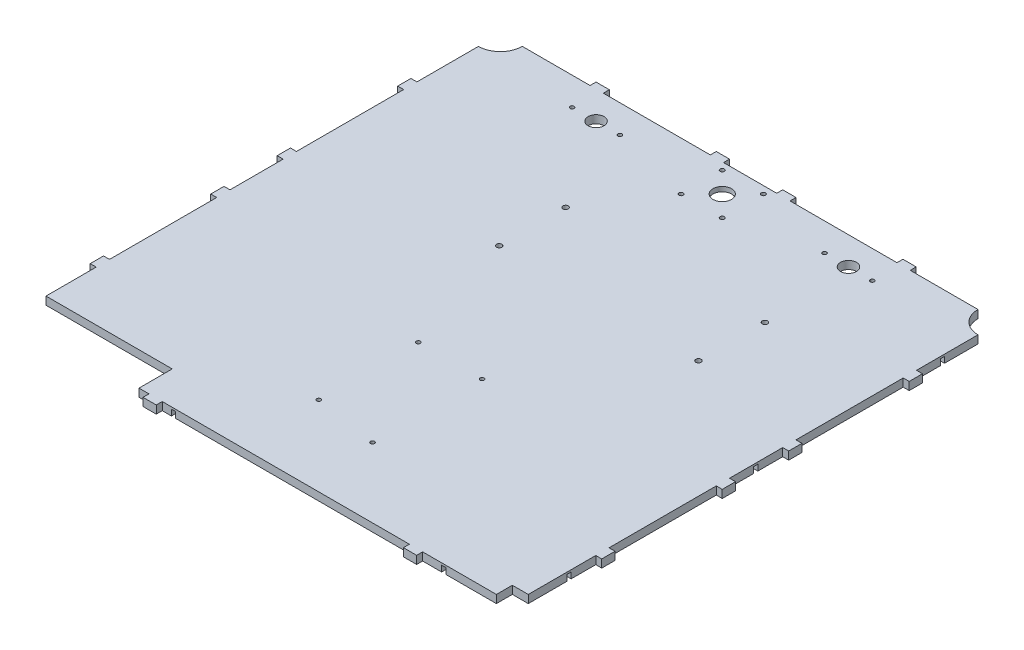
SolidWorks part; units mm, degrees
ref_plane "Alzado" through (0, 0, 0) normal (0, 0, 1) x (1, 0, 0)
ref_plane "Planta" through (0, 0, 0) normal (0, 1, 0) x (1, 0, 0)
ref_plane "Vista lateral" through (0, 0, 0) normal (1, 0, 0) x (0, 0, -1)
sketch "Croquis1" plane through (0, 0, 0) normal (0, 1, 0) x (1, 0, 0)
  line L0 (0, 0) -> (67.5, 0)
  line L1 (188, 367) -> (188, 375.2829) construction
  line L4 (77.5, 0) -> (102.5, 0)
  line L5 (0, 0) -> (0, 62.8)
  line L6 (0, 62.8) -> (-4.5, 62.8)
  line L7 (-4.5, 62.8) -> (-4.5, 72.8)
  line L8 (-4.5, 72.8) -> (0, 72.8)
  line L9 (0, 72.8) -> (0, 153.5)
  line L10 (0, 153.5) -> (-4.5, 153.5)
  line L11 (-4.5, 153.5) -> (-4.5, 163.5)
  line L12 (-4.5, 163.5) -> (0, 163.5)
  line L13 (0, 163.5) -> (0, 203.5)
  line L14 (0, 183.5) -> (180.5, 183.5) construction
  line L15 (188, 367) -> (188, 0) construction
  line L16 (-4.5, 203.5) -> (0, 203.5)
  line L17 (-4.5, 213.5) -> (-4.5, 203.5)
  line L18 (0, 213.5) -> (-4.5, 213.5)
  line L19 (0, 294.2) -> (0, 213.5)
  line L20 (-4.5, 294.2) -> (0, 294.2)
  line L21 (-4.5, 304.2) -> (-4.5, 294.2)
  line L22 (0, 304.2) -> (-4.5, 304.2)
  line L23 (0, 304.2) -> (0, 350.5)
  line L24 (16.5, 367) -> (67.5, 367)
  line L25 (67.5, 367) -> (67.5, 371.5)
  line L26 (67.5, 371.5) -> (77.5, 371.5)
  line L27 (77.5, 371.5) -> (77.5, 367)
  line L28 (77.5, 367) -> (158, 367)
  line L29 (158, 367) -> (158, 371.5)
  line L30 (158, 371.5) -> (168, 371.5)
  line L31 (168, 371.5) -> (168, 367)
  line L32 (168, 367) -> (208, 367)
  line L33 (376, 163.5) -> (376, 203.5)
  line L34 (380.5, 163.5) -> (376, 163.5)
  line L35 (380.5, 153.5) -> (380.5, 163.5)
  line L36 (376, 153.5) -> (380.5, 153.5)
  line L37 (376, 72.8) -> (376, 153.5)
  line L38 (380.5, 72.8) -> (376, 72.8)
  line L39 (380.5, 62.8) -> (380.5, 72.8)
  line L40 (376, 62.8) -> (380.5, 62.8)
  line L41 (376, 0) -> (376, 62.8)
  line L42 (298.5, -4.5) -> (298.5, 0)
  line L43 (308.5, -4.5) -> (298.5, -4.5)
  line L44 (308.5, 0) -> (308.5, -4.5)
  line L45 (376, 0) -> (308.5, 0)
  line L46 (208, 371.5) -> (208, 367)
  line L47 (218, 371.5) -> (208, 371.5)
  line L48 (218, 367) -> (218, 371.5)
  line L49 (298.5, 367) -> (218, 367)
  line L50 (298.5, 371.5) -> (298.5, 367)
  line L51 (308.5, 371.5) -> (298.5, 371.5)
  line L52 (308.5, 367) -> (308.5, 371.5)
  line L53 (359.5, 367) -> (308.5, 367)
  line L54 (376, 350.5) -> (376, 304.2)
  line L55 (376, 304.2) -> (380.5, 304.2)
  line L56 (380.5, 304.2) -> (380.5, 294.2)
  line L57 (380.5, 294.2) -> (376, 294.2)
  line L58 (376, 294.2) -> (376, 213.5)
  line L59 (376, 213.5) -> (380.5, 213.5)
  line L60 (380.5, 213.5) -> (380.5, 203.5)
  line L61 (380.5, 203.5) -> (376, 203.5)
  line L62 (102.5, 0) -> (102.5, 14.5062) construction
  line L63 (112.5, 0) -> (298.5, 0)
  line L64 (67.5, 0) -> (77.5, 0)
  line L65 (102.5, 0) -> (102.5, -4.5)
  line L66 (102.5, -4.5) -> (112.5, -4.5)
  line L67 (112.5, 0) -> (112.5, -4.5)
  arc A0 (0, 350.5) -> (16.5, 367) centre (0, 367) ccw
  arc A1 (376, 350.5) -> (359.5, 367) centre (376, 367) cw
  dimension "D8" = 33
  dimension "D14" = 46.3
  dimension "D2" = 20
  dimension "D5" = 62.8
  dimension "D6" = 4.5
  dimension "D7" = 10
  dimension "D9" = 10
  dimension "D10" = 20
  dimension "D11" = 51
  dimension "D12" = 10
  dimension "D13" = 4.5
  dimension "D15" = 10
  dimension "D16" = 16.5
  dimension "D17" = 16.5
  dimension "D18" = 25
  dimension "D19" = 10
  dimension "Ancho_panel" = 385
extrude "Saliente-Extruir1" add sketch "Croquis1" against normal blind 6
sketch "Croquis3" plane through (0, -6, 0) normal (0, -1, 0) x (1, 0, 0)
  line L0 (324.3519, 0) -> (324.3519, -11.6932) construction
  line L1 (325.9019, -6.5002) -> (325.9019, 0)
  line L2 (327.1922, -8.0283) -> (327.1922, -9.5783)
  line L3 (322.2204, -10.8802) -> (322.3896, -10.8802)
  line L4 (325.9019, 0) -> (322.8019, 0)
  line L5 (321.5115, -8.0283) -> (321.5115, -9.5783)
  line L6 (326.4834, -10.8802) -> (326.3141, -10.8802)
  line L7 (322.8019, -6.5002) -> (322.8019, 0)
  line L8 (0, -323.9093) -> (6.5002, -323.9093) construction
  line L9 (324.3519, -11.6932) -> (324.3519, 0.5178) construction
  line L10 (188, 0) -> (188, -367) construction
  line L11 (324.3519, -367) -> (324.3519, -355.3068) construction
  line L12 (208, -367) -> (168, -367) construction
  line L13 (322.8019, -360.4998) -> (322.8019, -367)
  line L14 (8.0283, -326.7496) -> (9.5783, -326.7496)
  line L15 (10.8802, -321.7778) -> (10.8802, -321.947)
  line L16 (6.5002, -322.3593) -> (0, -322.3593)
  line L17 (6.5002, -325.4593) -> (0, -325.4593)
  line L18 (10.8802, -326.0408) -> (10.8802, -325.8715)
  line L19 (0, -323.9093) -> (11.6932, -323.9093) construction
  line L20 (321.5115, -358.9717) -> (321.5115, -357.4217)
  line L21 (0, -322.3593) -> (0, -325.4593)
  line L22 (0, -42.91) -> (11.6932, -42.91) construction
  line L23 (6.5002, -41.36) -> (0, -41.36)
  line L24 (10.8802, -45.0415) -> (10.8802, -44.8722)
  line L25 (8.0283, -40.0697) -> (9.5783, -40.0697)
  line L26 (0, -44.46) -> (0, -41.36)
  line L27 (10.8802, -40.7785) -> (10.8802, -40.9478)
  line L28 (8.0283, -45.7503) -> (9.5783, -45.7503)
  line L29 (6.5002, -44.46) -> (0, -44.46)
  line L30 (326.4834, -356.1198) -> (326.3141, -356.1198)
  line L31 (8.0283, -321.0689) -> (9.5783, -321.0689)
  line L32 (121.0007, 0) -> (121.0007, -11.6932) construction
  line L33 (0, -183.2411) -> (376, -183.2411) construction
  line L34 (322.8019, -367) -> (325.9019, -367)
  line L35 (327.1922, -358.9717) -> (327.1922, -357.4217)
  line L36 (8.0283, -186.246) -> (9.5783, -186.246)
  line L37 (10.8802, -181.2741) -> (10.8802, -181.4434)
  line L38 (6.5002, -181.8556) -> (0, -181.8556)
  line L39 (6.5002, -184.9556) -> (0, -184.9556)
  line L40 (10.8802, -185.5371) -> (10.8802, -185.3679)
  line L41 (0, -183.4056) -> (11.6932, -183.4056) construction
  line L42 (0, -181.8556) -> (0, -184.9556)
  line L43 (8.0283, -180.5653) -> (9.5783, -180.5653)
  line L44 (122.5507, -6.5002) -> (122.5507, 0)
  line L45 (123.841, -8.0283) -> (123.841, -9.5783)
  line L46 (118.8692, -10.8802) -> (119.0384, -10.8802)
  line L47 (122.5507, 0) -> (119.4507, 0)
  line L48 (118.1603, -8.0283) -> (118.1603, -9.5783)
  line L49 (123.1322, -10.8802) -> (122.9629, -10.8802)
  line L50 (376, -42.7364) -> (364.3068, -42.7364) construction
  line L51 (369.4998, -44.2864) -> (376, -44.2864)
  line L52 (367.9717, -45.5768) -> (366.4217, -45.5768)
  line L53 (365.1198, -40.6049) -> (365.1198, -40.7742)
  line L54 (376, -44.2864) -> (376, -41.1864)
  line L55 (367.9717, -39.8961) -> (366.4217, -39.8961)
  line L56 (365.1198, -44.8679) -> (365.1198, -44.6987)
  line L57 (369.4998, -41.1864) -> (376, -41.1864)
  line L58 (376, -183.2411) -> (364.3068, -183.2411) construction
  line L59 (367.9717, -180.4008) -> (366.4217, -180.4008)
  line L60 (376, -181.6911) -> (376, -184.7911)
  line L61 (365.1198, -185.3726) -> (365.1198, -185.2033)
  line L62 (369.4998, -184.7911) -> (376, -184.7911)
  line L63 (369.4998, -181.6911) -> (376, -181.6911)
  line L64 (365.1198, -181.1096) -> (365.1198, -181.2788)
  line L65 (367.9717, -186.0814) -> (366.4217, -186.0814)
  line L66 (376, -323.728) -> (364.3068, -323.728) construction
  line L67 (369.4998, -325.278) -> (376, -325.278)
  line L68 (365.1198, -321.5965) -> (365.1198, -321.7657)
  line L69 (367.9717, -326.5683) -> (366.4217, -326.5683)
  line L70 (376, -322.178) -> (376, -325.278)
  line L71 (365.1198, -325.8594) -> (365.1198, -325.6902)
  line L72 (367.9717, -320.8876) -> (366.4217, -320.8876)
  line L73 (369.4998, -322.178) -> (376, -322.178)
  line L74 (324.3519, -355.9508) -> (324.3519, -367) construction
  line L75 (51.6481, -367) -> (51.6481, -355.3068) construction
  line L76 (50.0981, -360.4998) -> (50.0981, -367)
  line L77 (48.8078, -358.9717) -> (48.8078, -357.4217)
  line L78 (53.7796, -356.1198) -> (53.6104, -356.1198)
  line L79 (50.0981, -367) -> (53.1981, -367)
  line L80 (54.4885, -358.9717) -> (54.4885, -357.4217)
  line L81 (51.6481, -355.9508) -> (51.6481, -367) construction
  line L82 (51.6481, 0.5178) -> (51.6481, -24.8622) construction
  line L83 (322.2204, -356.1198) -> (322.3896, -356.1198)
  line L84 (119.4507, -6.5002) -> (119.4507, 0)
  line L85 (121.0007, -11.6932) -> (121.0007, 0) construction
  line L86 (325.9019, -360.4998) -> (325.9019, -367)
  line L87 (324.3519, -355.3068) -> (324.3519, -367.5178) construction
  line L88 (49.5166, -356.1198) -> (49.6859, -356.1198)
  line L89 (53.1981, -360.4998) -> (53.1981, -367)
  line L90 (51.6481, -355.3068) -> (51.6481, -367.5178) construction
  line L96 (51.6481, -355.9508) -> (51.6481, -367) construction
  arc A0 (327.1922, -8.0283) -> (325.9019, -6.5002) centre (325.6422, -8.0283) ccw
  arc A1 (322.3896, -10.8802) -> (326.3141, -10.8802) centre (324.3519, -8.9187) ccw
  arc A2 (322.2204, -10.8802) -> (321.5115, -9.5783) centre (323.0615, -9.5783) cw
  arc A3 (326.4834, -10.8802) -> (327.1922, -9.5783) centre (325.6422, -9.5783) ccw
  arc A4 (321.5115, -8.0283) -> (322.8019, -6.5002) centre (323.0615, -8.0283) cw
  arc A5 (8.0283, -321.0689) -> (6.5002, -322.3593) centre (8.0283, -322.6189) ccw
  arc A6 (8.0283, -326.7496) -> (6.5002, -325.4593) centre (8.0283, -325.1996) cw
  arc A7 (10.8802, -326.0408) -> (9.5783, -326.7496) centre (9.5783, -325.1996) cw
  arc A8 (10.8802, -321.7778) -> (9.5783, -321.0689) centre (9.5783, -322.6189) ccw
  arc A9 (10.8802, -325.8715) -> (10.8802, -321.947) centre (8.9187, -323.9093) ccw
  arc A10 (8.0283, -40.0697) -> (6.5002, -41.36) centre (8.0283, -41.6197) ccw
  arc A11 (10.8802, -45.0415) -> (9.5783, -45.7503) centre (9.5783, -44.2003) cw
  arc A12 (10.8802, -40.7785) -> (9.5783, -40.0697) centre (9.5783, -41.6197) ccw
  arc A13 (10.8802, -40.9478) -> (10.8802, -44.8722) centre (8.9187, -42.91) cw
  arc A14 (8.0283, -45.7503) -> (6.5002, -44.46) centre (8.0283, -44.2003) cw
  arc A15 (8.0283, -180.5653) -> (6.5002, -181.8556) centre (8.0283, -182.1153) ccw
  arc A16 (8.0283, -186.246) -> (6.5002, -184.9556) centre (8.0283, -184.696) cw
  arc A17 (10.8802, -185.5371) -> (9.5783, -186.246) centre (9.5783, -184.696) cw
  arc A18 (10.8802, -181.2741) -> (9.5783, -180.5653) centre (9.5783, -182.1153) ccw
  arc A19 (10.8802, -185.3679) -> (10.8802, -181.4434) centre (8.9187, -183.4056) ccw
  arc A20 (123.841, -8.0283) -> (122.5507, -6.5002) centre (122.291, -8.0283) ccw
  arc A21 (119.0384, -10.8802) -> (122.9629, -10.8802) centre (121.0007, -8.9187) ccw
  arc A22 (118.8692, -10.8802) -> (118.1603, -9.5783) centre (119.7103, -9.5783) cw
  arc A23 (123.1322, -10.8802) -> (123.841, -9.5783) centre (122.291, -9.5783) ccw
  arc A24 (118.1603, -8.0283) -> (119.4507, -6.5002) centre (119.7103, -8.0283) cw
  arc A25 (367.9717, -45.5768) -> (369.4998, -44.2864) centre (367.9717, -44.0268) ccw
  arc A26 (365.1198, -40.7742) -> (365.1198, -44.6987) centre (367.0813, -42.7364) ccw
  arc A27 (365.1198, -40.6049) -> (366.4217, -39.8961) centre (366.4217, -41.4461) cw
  arc A28 (365.1198, -44.8679) -> (366.4217, -45.5768) centre (366.4217, -44.0268) ccw
  arc A29 (367.9717, -39.8961) -> (369.4998, -41.1864) centre (367.9717, -41.4461) cw
  arc A30 (365.1198, -185.2033) -> (365.1198, -181.2788) centre (367.0813, -183.2411) cw
  arc A31 (365.1198, -181.1096) -> (366.4217, -180.4008) centre (366.4217, -181.9508) cw
  arc A32 (365.1198, -185.3726) -> (366.4217, -186.0814) centre (366.4217, -184.5314) ccw
  arc A33 (367.9717, -186.0814) -> (369.4998, -184.7911) centre (367.9717, -184.5314) ccw
  arc A34 (367.9717, -180.4008) -> (369.4998, -181.6911) centre (367.9717, -181.9508) cw
  arc A35 (367.9717, -326.5683) -> (369.4998, -325.278) centre (367.9717, -325.0183) ccw
  arc A36 (365.1198, -321.5965) -> (366.4217, -320.8876) centre (366.4217, -322.4376) cw
  arc A37 (365.1198, -325.8594) -> (366.4217, -326.5683) centre (366.4217, -325.0183) ccw
  arc A38 (365.1198, -325.6902) -> (365.1198, -321.7657) centre (367.0813, -323.728) cw
  arc A39 (367.9717, -320.8876) -> (369.4998, -322.178) centre (367.9717, -322.4376) cw
  arc A40 (48.8078, -358.9717) -> (50.0981, -360.4998) centre (50.3578, -358.9717) ccw
  arc A41 (53.6104, -356.1198) -> (49.6859, -356.1198) centre (51.6481, -358.0813) ccw
  arc A42 (53.7796, -356.1198) -> (54.4885, -357.4217) centre (52.9385, -357.4217) cw
  arc A43 (49.5166, -356.1198) -> (48.8078, -357.4217) centre (50.3578, -357.4217) ccw
  arc A44 (54.4885, -358.9717) -> (53.1981, -360.4998) centre (52.9385, -358.9717) cw
  arc A50 (321.5115, -358.9717) -> (322.8019, -360.4998) centre (323.0615, -358.9717) ccw
  arc A51 (326.3141, -356.1198) -> (322.3896, -356.1198) centre (324.3519, -358.0813) ccw
  arc A52 (326.4834, -356.1198) -> (327.1922, -357.4217) centre (325.6422, -357.4217) cw
  arc A53 (322.2204, -356.1198) -> (321.5115, -357.4217) centre (323.0615, -357.4217) ccw
  arc A54 (327.1922, -358.9717) -> (325.9019, -360.4998) centre (325.6422, -358.9717) cw
  dimension "D4" = 1.55
  dimension "D6" = 0.4122
  dimension "D8" = 1.5281
  dimension "D10" = 0.1692
  dimension "D23" = 6.5002
  dimension "D25" = 1.55
  dimension "D24" = 1.55
  dimension "D31" = 1.55
  dimension "D33" = 11.6932
  dimension "D26" = 1.55
  dimension "D5" = 1.55
  dimension "D1" = 6.5002
  dimension "D7" = 1.55
  dimension "D9" = 1.55
  dimension "D11" = 11.6932
  dimension "D27" = 4.38
  dimension "D28" = 0.4122
  dimension "D29" = 1.55
  dimension "D30" = 1.5281
  dimension "D32" = 0.1692
  dimension "D34" = 51.6481
extrude "Cortar-Extruir1" cut sketch "Croquis3" against normal blind 4.5
sketch "Croquis5" plane through (0, 0, 0) normal (0, 1, 0) x (1, 0, 0)
  line L0 (188, 367) -> (188, 346) construction
  line L1 (0, 0) -> (12, 0)
  line L2 (0, 0) -> (0, 12)
  line L3 (0, 12) -> (12, 12)
  line L4 (12, 0) -> (12, 12)
  line L5 (376, 0) -> (364, 0)
  line L6 (376, 0) -> (376, 12)
  line L7 (376, 12) -> (364, 12)
  line L8 (364, 0) -> (364, 12)
  line L9 (158, 367) -> (77.5, 367) construction
  line L10 (67.5, 367) -> (16.5, 367) construction
  line L11 (208, 367) -> (168, 367) construction
  line L12 (172.5, 361.5) -> (172.5, 346) construction
  line L13 (172.5, 346) -> (188, 346) construction
  line L14 (188, 346) -> (73.5, 346) construction
  circle A0 centre (188, 346) radius 7
  circle A1 centre (172.5, 361.5) radius 1.6
  circle A2 centre (203.5, 361.5) radius 1.6
  circle A3 centre (203.5, 330.5) radius 1.6
  circle A4 centre (172.5, 330.5) radius 1.6
  circle A5 centre (93, 346) radius 6
  circle A6 centre (111, 346) radius 1.5
  circle A7 centre (75, 346) radius 1.5
  circle A8 centre (301, 346) radius 1.5
  circle A9 centre (265, 346) radius 1.5
  circle A10 centre (283, 346) radius 6
  dimension "D4" = 14
  dimension "D5" = 3.2
  dimension "D9" = 3
  dimension "D8" = 12
  dimension "D11" = 3
  dimension "D1" = 12
  dimension "D2" = 12
  dimension "D3" = 21
  dimension "D6" = 15.5
  dimension "D7" = 15.5
  dimension "D10" = 18
  dimension "D12" = 18
  dimension "D13" = 95
  dimension "D16" = 21
  dimension "D17" = 21
extrude "Cortar-Extruir2" cut sketch "Croquis5" against normal up to surface (6 mm away) up to face at (193.3419, -6, -193.3919)
sketch "Croquis7" plane through (0, 0, 0) normal (0, 1, 0) x (1, 0, 0)
  line L1 (12, 0) -> (102.5, 0) construction
  line L3 (95, 0) -> (0, 0)
  line L4 (95, 0) -> (95, 25)
  line L5 (95, 25) -> (0, 25)
  line L6 (0, 0) -> (0, 25)
  line L7 (0, 62.8) -> (0, 12) construction
  circle A0 centre (137.7441, 278.3503) radius 2
  circle A1 centre (137.7441, 228.3503) radius 2
  circle A2 centre (287.7441, 228.3503) radius 2
  circle A3 centre (287.7441, 278.3503) radius 2
  circle A4 centre (218.2736, 134.9894) radius 1.5
  circle A5 centre (170.2736, 134.9894) radius 1.5
  circle A6 centre (218.2736, 52.4894) radius 1.5
  circle A7 centre (170.2736, 59.9894) radius 1.5
  dimension "D5" = 4
  dimension "D6" = 4
  dimension "D7" = 4
  dimension "D8" = 4
  dimension "D1" = 3
  dimension "D4" = 3
  dimension "D10" = 3
  dimension "D12" = 3
  dimension "D2" = 50
  dimension "D3" = 50
  dimension "D9" = 48
  dimension "D11" = 82.5
  dimension "D13" = 75
  dimension "D14" = 95
  dimension "D15" = 25
  dimension "D16" = 150
extrude "Cortar-Extruir4" cut sketch "Croquis7" against normal blind 10
sketch "Croquis8" plane through (0, -6, 0) normal (0, -1, 0) x (1, 0, 0)
  circle A2 centre (265, -346) radius 1.5 construction
  circle A4 centre (188, -346) radius 7 construction
  circle A5 centre (188, -346) radius 7
  circle A6 centre (265, -346) radius 1.5
  circle A7 centre (188, -346) radius 11
  circle A8 centre (111, -346) radius 4.5
  circle A9 centre (75, -346) radius 4.5
  circle A10 centre (265, -346) radius 4.5
  circle A11 centre (301, -346) radius 4.5
  dimension "D1" = 95
  dimension "D2" = 95
extrude "Cortar-Extruir5" cut sketch "Croquis8" against normal blind 2.5
equation "\"Ancho_panel\"= 385'Ancho del panel"
equation "\"Alto_panel\"= 420'Alto del panel izquierdo"
equation "\"Altura_base_taladros\"= 70'Alto taladros de la base eje Z"
equation "\"Altura_superior_taladros\"= 8mm'Distancia taladros a top"
equation "\"Distancia_vert_entre_horizontales_ensambles\"= \"Alto_panel\" - \"Altura_base_taladros\" - \"Altura_superior_taladros\"'Distancia vertical entre horizontales de ensambles"
equation "\"Latrales_separacion_barras_a_escalon_bajo\"= 12.5'Separación entre las barras y el escalón inferior de la parte superior"
equation "\"Espacio_tensor_correa_motor\"= 8.5mm'Espacio para mover el motor en vertical y tensar la correa"
equation "\"Ancho_panel_interior\"= \"Ancho_panel\" - 9mm'Ancho panel interior"
equation "\"Fondo_panel_interior\"= \"Ancho_panel\" - 9mm'Fondo panel interior"
